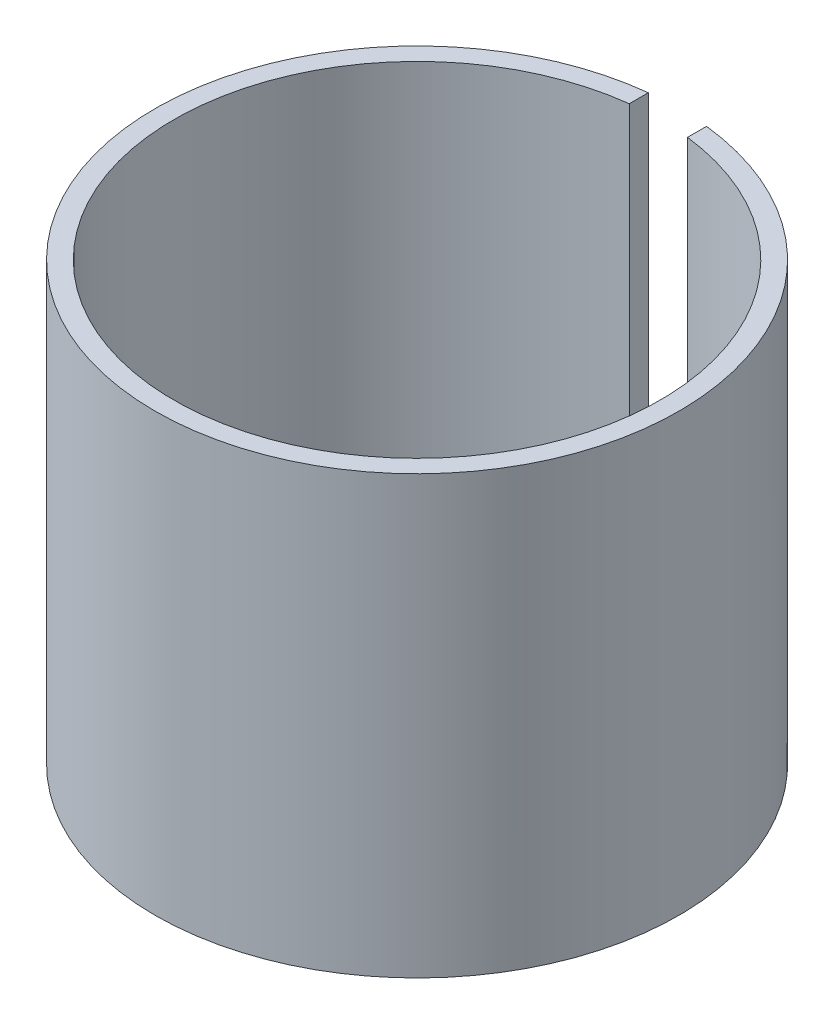
SolidWorks part; units mm, degrees
material "Epoxy, Unfilled"
ref_plane "Front Plane" through (0, 0, 0) normal (0, 0, 1) x (1, 0, 0)
ref_plane "Top Plane" through (0, 0, 0) normal (0, 1, 0) x (1, 0, 0)
ref_plane "Right Plane" through (0, 0, 0) normal (1, 0, 0) x (0, 0, -1)
sketch "Sketch1" plane through (0, 0, 0) normal (0, 1, 0) x (1, 0, 0)
  circle A0 centre (0, 0) radius 18
  dimension "D1" = 36
extrude "Boss-Extrude1" add sketch "Sketch1" along normal blind 5
sketch "Sketch2" plane through (0, 5, 0) normal (0, 1, 0) x (1, 0, 0)
  circle A0 centre (0, 0) radius 18
  circle A1 centre (0, 0) radius 16.7
  dimension "D1" = 33.4
extrude "Boss-Extrude2" add sketch "Sketch2" along normal blind 25
sketch "Sketch3" plane through (0, 30, 0) normal (0, 1, 0) x (1, 0, 0)
  line L0 (-2, 14.3872) -> (2, 14.3872)
  line L1 (-2, 14.3872) -> (-2, 19.0128)
  line L2 (2, 14.3872) -> (2, 19.0128)
  line L3 (-2, 19.0128) -> (2, 19.0128)
  line L4 (-2, 14.3872) -> (2, 19.0128) construction
  line L5 (2, 14.3872) -> (-2, 19.0128) construction
  circle A0 centre (0, 0) radius 16.7 construction
  circle A1 centre (0, 0) radius 16.7 construction
  point P0 (0, 16.7)
  point P1 (0, 16.7)
  dimension "D1" = 4
extrude "Cut-Extrude1" cut sketch "Sketch3" against normal up to surface (25 mm away) up to face at (0, 5, 16.7)
sketch "Sketch4" plane through (0, 5, 0) normal (0, 1, 0) x (1, 0, 0)
  circle A0 centre (0, 15) radius 2
  point P2 (0, 15.5803)
  dimension "D1" = 4
  dimension "D2" = 15
sketch "Sketch5" plane through (0, 0, 0) normal (0, -1, 0) x (-1, 0, 0)
  circle A0 centre (0, 10) radius 2
  point P2 (0, 0)
  dimension "D1" = 4
  dimension "D2" = 10
loft "Cut-Loft1" cut profiles "Sketch5", "Sketch4" connector at (-1.7125, 0, -8.9668) connector at (-1.5093, 5, -13.6878)
